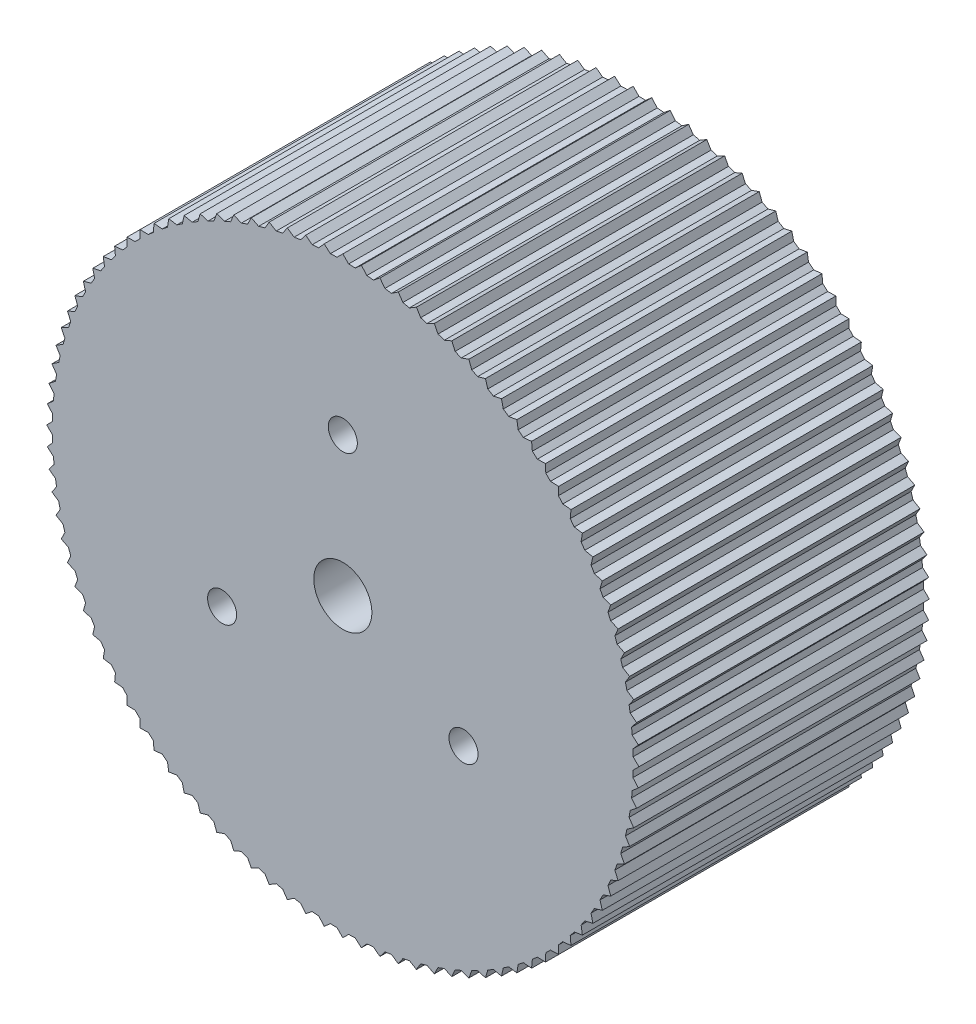
SolidWorks part; units mm, degrees
ref_plane "Front" through (0, 0, 0) normal (0, 0, 1) x (1, 0, 0)
ref_plane "Top" through (0, 0, 0) normal (0, 1, 0) x (1, 0, 0)
ref_plane "Right" through (0, 0, 0) normal (1, 0, 0) x (0, 0, -1)
sketch "Sketch1" plane through (0, 0, 0) normal (0, 0, 1) x (1, 0, 0)
  circle A0 centre (0, 0) radius 25
  dimension "D1" = 50
extrude "Boss-Extrude1" add sketch "Sketch1" along normal blind 25
sketch "Sketch6" plane through (0, 0, 0) normal (0, 0, -1) x (-1, 0, 0)
  circle A0 centre (0, 0) radius 10
  dimension "D1" = 20
extrude "Boss-Extrude3" add sketch "Sketch6" along normal offset from surface (9 mm away) 1
sketch "Sketch2" plane through (0, 0, -9) normal (0, 0, -1) x (-1, 0, 0)
  circle A0 centre (0, 0) radius 3.6
extrude "Cut-Extrude1" cut sketch "Sketch2" against normal blind 2.4
sketch "Sketch3" plane through (0, 0, -6.6) normal (0, 0, -1) x (-1, 0, 0)
  circle A0 centre (0, 0) radius 2.5
extrude "Cut-Extrude2" cut sketch "Sketch3" against normal through all
sketch "Sketch5" plane through (0, 0, 0) normal (0, 0, -1) x (-1, 0, 0)
  line L0 (24.995, 0.5) -> (25.495, 0)
  line L1 (25.495, 0) -> (24.995, -0.5)
  line L2 (24.995, -0.5) -> (24.7063, -0.5)
  line L3 (24.7063, -0.5) -> (24.7063, 0.5)
  line L4 (24.7063, 0.5) -> (24.995, 0.5)
  line L5 (25.495, 0) -> (0, 0) construction
  circle A1 centre (0, 0) radius 25 construction
  dimension "D1" = 90
  dimension "D2" = 90
  dimension "D3" = 90
  dimension "D4" = 0.5
  dimension "D5" = 45
  dimension "D6" = 90
extrude "Boss-Extrude2" add sketch "Sketch5" against normal through all
pattern_circular "CirPattern1" count 100 over 360 about axis through (0, 0, 0) along (0, 0, 1) of "Boss-Extrude2"
sketch "Sketch7" plane through (0, 0, 25) normal (0, 0, 1) x (1, 0, 0)
  circle A0 centre (0, 12) radius 1.25
  circle A1 centre (-10.3923, -6) radius 1.25
  circle A2 centre (10.3923, -6) radius 1.25
extrude "Cut-Extrude3" cut sketch "Sketch7" against normal blind 15
